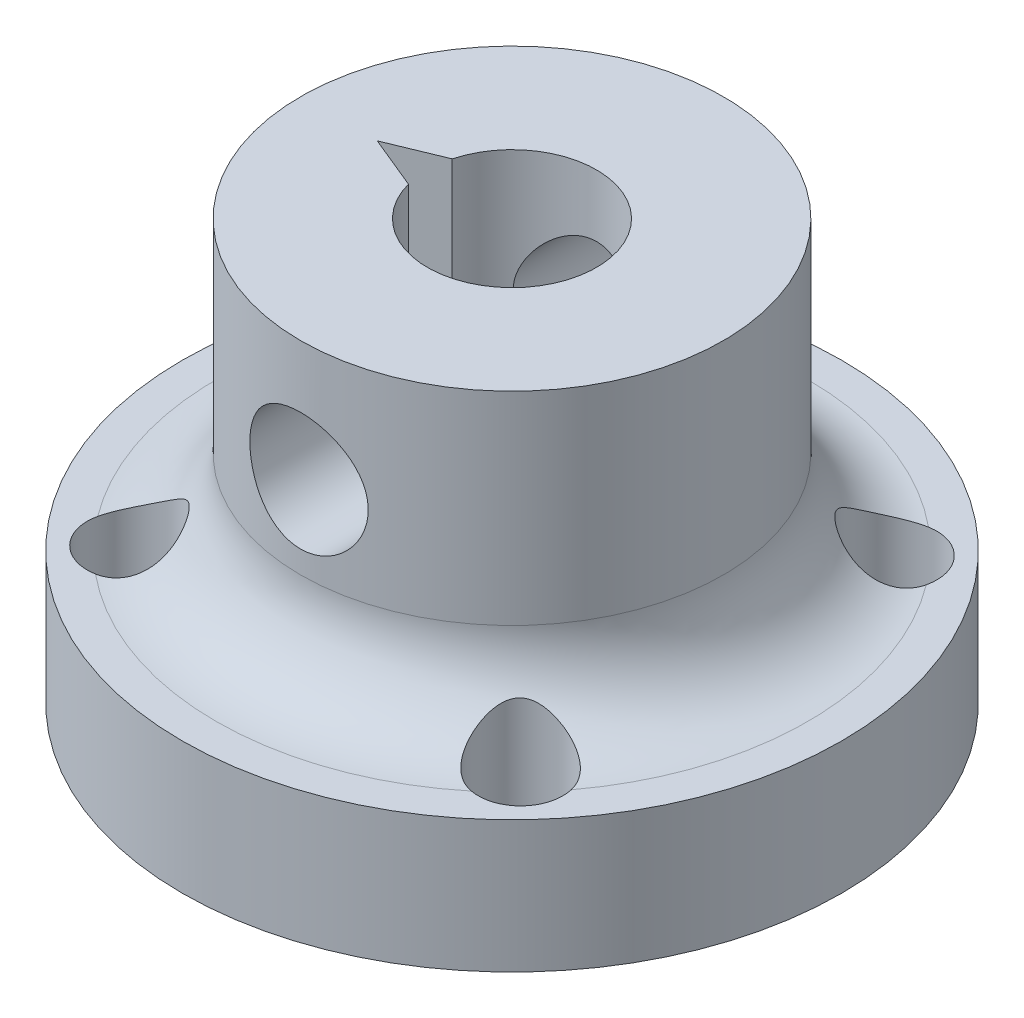
SolidWorks part; units mm, degrees
ref_plane "Front Plane" through (0, 0, 0) normal (0, 0, 1) x (1, 0, 0)
ref_plane "Top Plane" through (0, 0, 0) normal (0, 1, 0) x (1, 0, 0)
ref_plane "Right Plane" through (0, 0, 0) normal (1, 0, 0) x (0, 0, -1)
sketch "Sketch1" plane through (0, 0, 0) normal (0, 1, 0) x (1, 0, 0)
  line L1 (-5.7823, -5.5286) -> (5.7823, -5.5286)
  line L2 (-5.7823, -5.5286) -> (-5.7823, 5.5286)
  line L3 (-5.7823, 5.5286) -> (5.7823, 5.5286)
  line L4 (5.7823, -5.5286) -> (5.7823, 5.5286)
  line L5 (-5.7823, -5.5286) -> (5.7823, 5.5286) construction
  line L6 (-5.7823, 5.5286) -> (5.7823, -5.5286) construction
  circle A0 centre (0, 0) radius 9.75
  circle A1 centre (-5.7823, 5.5286) radius 1.25
  circle A2 centre (-5.7823, -5.5286) radius 1.25
  circle A3 centre (5.7823, -5.5286) radius 1.25
  circle A4 centre (5.7823, 5.5286) radius 1.25
  dimension "D1" = 19.5
  dimension "D3" = 2.5
  dimension "D4" = 2.5
  dimension "D5" = 2.5
  dimension "D6" = 2.5
  dimension "D2" = 16
extrude "Boss-Extrude2" add sketch "Sketch1" along normal blind 2 contours A0 A4 L4 A3 L1 A2 L2 A1 L3 | A4 L3 A1 L2 A2 L1 A3 L4 region at (0, 0, 0) region at (-9.4742, 0, 0)
sketch "Sketch2" plane through (0, 2, 0) normal (0, 1, 0) x (1, 0, 0)
  circle A0 centre (0, 0) radius 6.25
  dimension "D1" = 12.5
extrude "Boss-Extrude3" add sketch "Sketch2" along normal blind 8.5
sketch "Sketch4" plane through (0, 10.5, 0) normal (0, 1, 0) x (1, 0, 0)
  circle A0 centre (0, 0) radius 2.5
  dimension "D1" = 5
extrude "Cut-Extrude1" cut sketch "Sketch4" against normal blind 7.5
sketch "Sketch5" plane through (0, 0, 0) normal (0, 0, 1) x (1, 0, 0)
  circle A0 centre (0, 6.9145) radius 1.75
  dimension "D1" = 3.5
extrude "Cut-Extrude2" cut sketch "Sketch5" against normal blind 6.75 and the other way blind 7.5
sketch "Sketch7" plane through (0, 0, 0) normal (0, -1, 0) x (1, 0, 0)
  circle A4 centre (0, 0) radius 9.75
  circle A5 centre (0, 0) radius 4.5
  circle A6 centre (-5.7823, 5.5286) radius 1.25
  circle A7 centre (5.7823, 5.5286) radius 1.25
  circle A8 centre (5.7823, -5.5286) radius 1.25
  circle A9 centre (-5.7823, -5.5286) radius 1.25
  point P0 (0, 0)
  dimension "D1" = 9
  dimension "D2" = 19.5
extrude "Boss-Extrude5" add sketch "Sketch7" along normal blind 1.9
sketch "Sketch9" plane through (0, 10.5, 0) normal (0, 1, 0) x (1, 0, 0)
  line L1 (-2.4148, -0.6473) -> (-2.4148, 0.6473)
  line L4 (-2.4148, 0.6473) -> (-3.9844, 0)
  line L5 (-3.9844, 0) -> (-2.4148, -0.6473)
  circle A1 centre (0, 0) radius 2.5 construction
  circle A2 centre (0, 0) radius 2.5 construction
extrude "Cut-Extrude3" cut sketch "Sketch9" against normal blind 8
fillet "Fillet1" radius 2.5 1 edges at (0, 2, 6.25)
